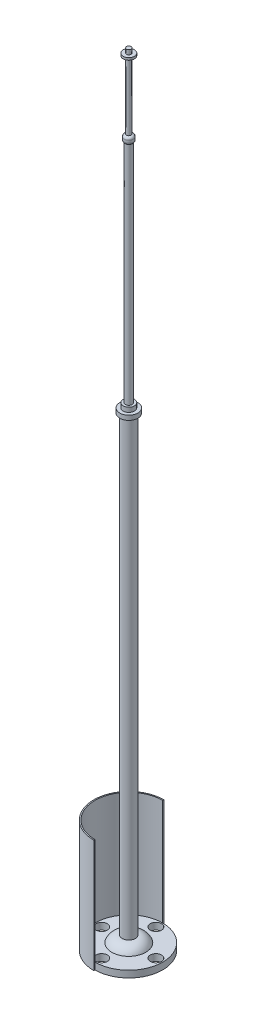
SolidWorks part; units mm, degrees
ref_plane "Front Plane" through (0, 0, 0) normal (0, 0, 1) x (1, 0, 0)
ref_plane "Top Plane" through (0, 0, 0) normal (0, 1, 0) x (1, 0, 0)
ref_plane "Right Plane" through (0, 0, 0) normal (1, 0, 0) x (0, 0, -1)
sketch "Sketch1" plane through (0, 0, 0) normal (0, 1, 0) x (1, 0, 0)
  circle A0 centre (0, 0) radius 15
  dimension "D1" = 30
extrude "Boss-Extrude1" add sketch "Sketch1" along normal blind 3
sketch "Sketch2" plane through (0, 3, 0) normal (0, 1, 0) x (1, 0, 0)
  circle A1 centre (0, 12) radius 2.5
  circle A2 centre (12, 0) radius 2.5
  circle A3 centre (0, -12) radius 2.5
  circle A4 centre (-12, 0) radius 2.5
  point P14 (0, 0)
  dimension "D1" = 12
  dimension "D2" = 5
  dimension "D4" = 4
extrude "Cut-Extrude1" cut sketch "Sketch2" against normal blind 3
sketch "Sketch3" plane through (0, 3, 0) normal (0, 1, 0) x (1, 0, 0)
  circle A0 centre (0, 0) radius 7.5
  dimension "D1" = 15
extrude "Boss-Extrude3" add sketch "Sketch3" along normal blind 3
fillet "Fillet1" radius 5 1 edges at (0, 6, 7.5)
sketch "Sketch4" plane through (0, 6, 0) normal (0, 1, 0) x (1, 0, 0)
  circle A0 centre (0, 0) radius 2.9174
extrude "Boss-Extrude4" add sketch "Sketch4" along normal blind 200
sketch "Sketch5" plane through (0, 206, 0) normal (0, 1, 0) x (1, 0, 0)
  circle A0 centre (0, 0) radius 4
  dimension "D1" = 8
extrude "Boss-Extrude5" add sketch "Sketch5" along normal blind 2
sketch "Sketch6" plane through (0, 208, 0) normal (0, 1, 0) x (1, 0, 0)
  circle A0 centre (0, 0) radius 2.5
  dimension "D1" = 5
extrude "Boss-Extrude6" add sketch "Sketch6" along normal blind 2
sketch "Sketch7" plane through (0, 210, 0) normal (0, 1, 0) x (1, 0, 0)
  circle A0 centre (0, 0) radius 1.5
  dimension "D1" = 3
extrude "Boss-Extrude7" add sketch "Sketch7" along normal blind 100
sketch "Sketch8" plane through (0, 310, 0) normal (0, 1, 0) x (1, 0, 0)
  circle A0 centre (0, 0) radius 2
  dimension "D1" = 4
extrude "Boss-Extrude9" add sketch "Sketch8" along normal blind 3
fillet "Fillet4" radius 1 2 edges at (0, 310, 2) (0, 313, 2)
sketch "Sketch9" plane through (0, 313, 0) normal (0, 1, 0) x (1, 0, 0)
  circle A0 centre (0, 0) radius 1
  dimension "D1" = 2
extrude "Boss-Extrude10" add sketch "Sketch9" along normal blind 30
sketch "Sketch10" plane through (0, 343, 0) normal (0, 1, 0) x (1, 0, 0)
  circle A0 centre (0, 0) radius 2.5
  dimension "D1" = 5
extrude "Boss-Extrude11" add sketch "Sketch10" along normal blind 1
sketch "Sketch11" plane through (0, 344, 0) normal (0, 1, 0) x (1, 0, 0)
  circle A0 centre (0, 0) radius 1
  dimension "D1" = 2
extrude "Boss-Extrude12" add sketch "Sketch11" along normal blind 2
sketch "Sketch12" plane through (0, 0, 0) normal (0, -1, 0) x (1, 0, 0)
  line L0 (0, 15.5) -> (0, 15)
  line L1 (0, -15) -> (0, -15.5)
  circle A0 centre (0, 0) radius 15
  circle A1 centre (0, 0) radius 15.5
  circle M6 centre (0, 0) radius 15
  dimension "D1" = 30
  dimension "D2" = 0.5
extrude "Boss-Extrude13" add sketch "Sketch12" against normal blind 50 contours L0 A1 L1 M6 region at (-0.3466, 0, 15.25)
